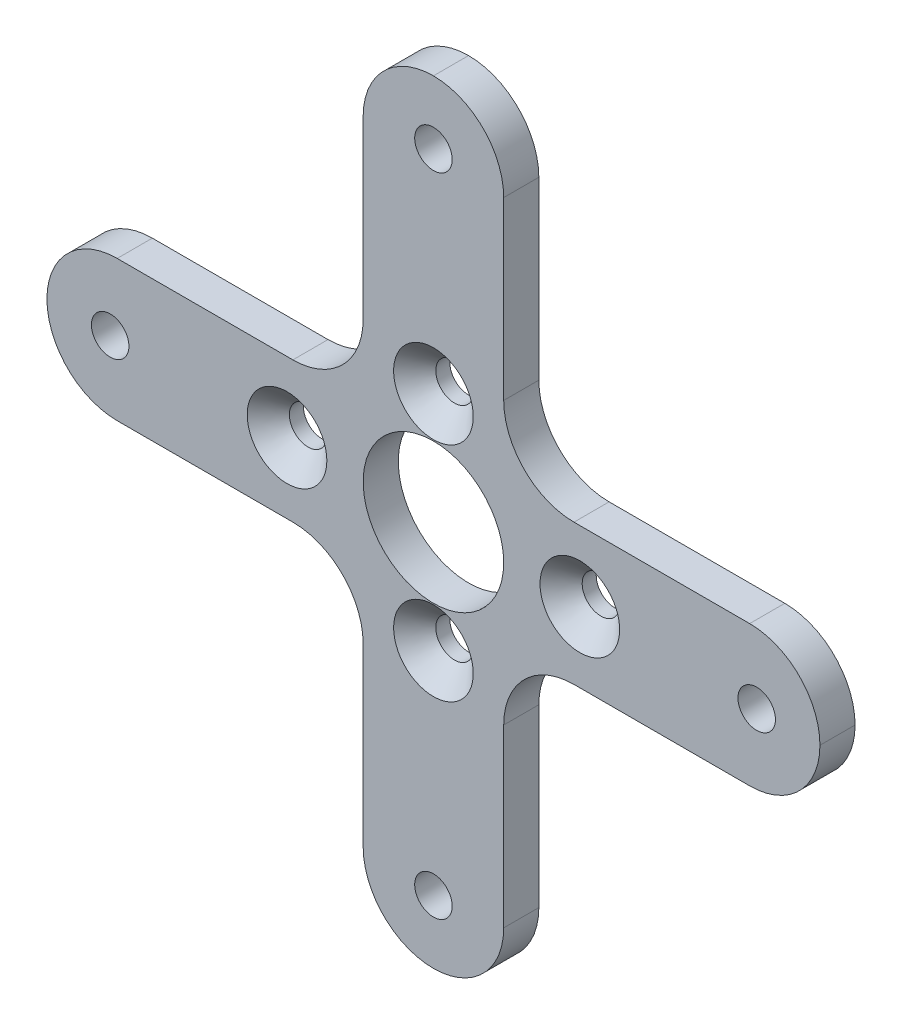
SolidWorks part; units mm, degrees
ref_plane "前视基准面" through (0, 0, 0) normal (0, 0, 1) x (1, 0, 0)
ref_plane "上视基准面" through (0, 0, 0) normal (0, 1, 0) x (1, 0, 0)
ref_plane "右视基准面" through (0, 0, 0) normal (1, 0, 0) x (0, 0, -1)
sketch "草图1" plane through (0, 0, 0) normal (0, 0, 1) x (1, 0, 0)
  line L0 (-6, 0) -> (6, 0)
  line L1 (6, 0) -> (6, -27)
  line L2 (6, -27) -> (33, -27)
  line L3 (33, -27) -> (33, -39)
  line L4 (33, -39) -> (6, -39)
  line L5 (6, -39) -> (6, -66)
  line L6 (6, -66) -> (-6, -66)
  line L7 (-6, -66) -> (-6, -39)
  line L8 (-6, -39) -> (-33, -39)
  line L9 (-33, -39) -> (-33, -27)
  line L10 (-33, -27) -> (-6, -27)
  line L11 (-6, -27) -> (-6, 0)
  circle A0 centre (0, -33) radius 27.6 construction
  circle A1 centre (0, -33) radius 12.5 construction
  circle A2 centre (0, -33) radius 9.5 construction
  circle A3 centre (0, -5.4) radius 1.6
  circle A4 centre (-27.6, -33) radius 1.6
  circle A5 centre (27.6, -33) radius 1.6
  circle A6 centre (0, -60.6) radius 1.6
  circle A7 centre (0, -23.5) radius 1.6
  circle A8 centre (12.5, -33) radius 1.6
  circle A9 centre (0, -42.5) radius 1.6
  circle A10 centre (-12.5, -33) radius 1.6
  circle A11 centre (0, -33) radius 6
  point P14 (33, -33)
  point P17 (0, 0)
  point P18 (0, -66)
  dimension "D1" = 55.2
  dimension "D2" = 19
  dimension "D3" = 25
  dimension "D4" = 3.2
  dimension "D5" = 3.2
  dimension "D6" = 12
  dimension "D7" = 12
  dimension "D8" = 27
extrude "凸台-拉伸1" add sketch "草图1" along normal blind 3
fillet "圆角1" radius 6 12 edges at (-6, -39, 1.5) (-6, -66, 1.5) (6, -66, 1.5) (6, -39, 1.5) (33, -39, 1.5) (33, -27, 1.5) (-6, 0, 1.5) (6, 0, 1.5) (6, -27, 1.5) (-6, -27, 1.5) (-33, -39, 1.5) (-33, -27, 1.5)
chamfer "倒角1" distance 1.8 angle 45 4 edges at (1.6, -23.5, 3) (1.6, -42.5, 3) (14.1, -33, 3) (-10.9, -33, 3)
